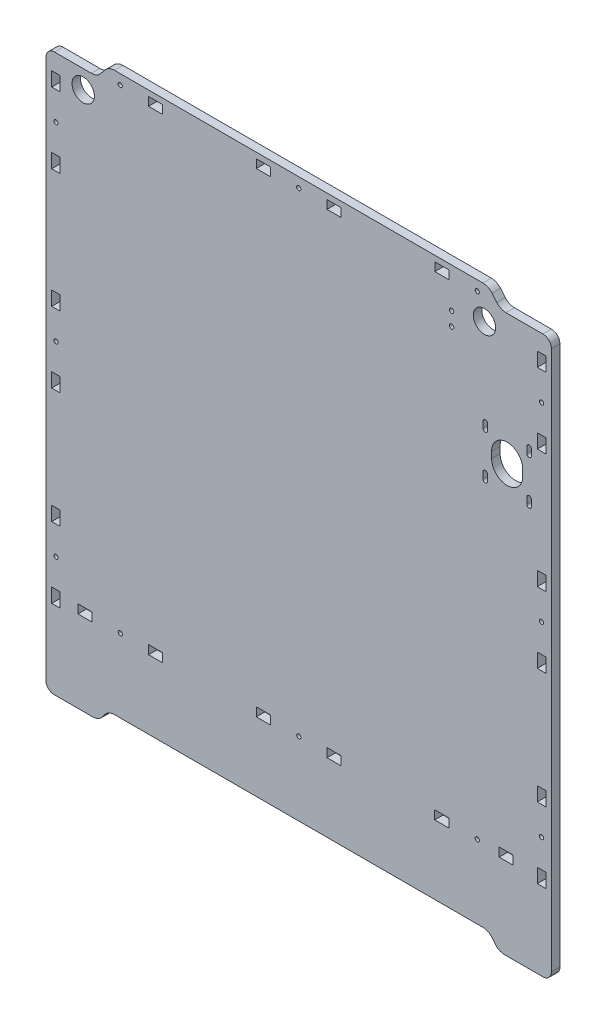
SolidWorks part; units mm, degrees
ref_plane "Спереди" through (0, 0, 0) normal (0, 0, 1) x (1, 0, 0)
ref_plane "Сверху" through (0, 0, 0) normal (0, 1, 0) x (1, 0, 0)
ref_plane "Справа" through (0, 0, 0) normal (1, 0, 0) x (0, 0, -1)
sketch "Эскиз1" plane through (0, 0, 0) normal (0, 0, 1) x (1, 0, 0)
  line L0 (133.6555, 83.4698) -> (133.6555, 87.9698)
  line L1 (133.6555, 118.9698) -> (133.6555, 114.4698)
  line L2 (130.4555, 83.4698) -> (130.4555, 87.9698)
  line L3 (158.5555, 98.9698) -> (158.5555, 103.4698)
  line L4 (130.4555, 118.9698) -> (130.4555, 114.4698)
  line L5 (161.4555, 118.9698) -> (161.4555, 114.4698)
  line L6 (164.6555, 118.9698) -> (164.6555, 114.4698)
  line L7 (136.5555, 98.9698) -> (136.5555, 103.4698)
  line L8 (161.4555, 83.4698) -> (161.4555, 87.9698)
  line L9 (164.6555, 83.4698) -> (164.6555, 87.9698)
  line L10 (-174.1809, 36.7423) -> (-174.1809, 46.7423)
  line L11 (106.3726, -142.2004) -> (96.3778, -142.2004)
  line L12 (96.3778, -142.2004) -> (96.3778, -136.0006)
  line L13 (96.3778, -136.0006) -> (106.3726, -136.0006)
  line L14 (106.3726, -136.0006) -> (106.3726, -142.2004)
  line L15 (151.7592, -142.2004) -> (141.91, -142.2004)
  line L16 (141.91, -142.2004) -> (141.91, -136.0006)
  line L17 (141.91, -136.0006) -> (151.7592, -136.0006)
  line L18 (151.7592, -136.0006) -> (151.7592, -142.2004)
  line L19 (-19.6709, 193.3023) -> (-29.6709, 193.3023)
  line L20 (-29.6709, 193.3023) -> (-29.6709, 199.3023)
  line L21 (-29.6709, 199.3023) -> (-19.6709, 199.3023)
  line L22 (-19.6709, 199.3023) -> (-19.6709, 193.3023)
  line L23 (30.3091, 193.3023) -> (20.3091, 193.3023)
  line L24 (20.3091, 193.3023) -> (20.3091, 199.3023)
  line L25 (20.3091, 199.3023) -> (30.3091, 199.3023)
  line L26 (30.3091, 199.3023) -> (30.3091, 193.3023)
  line L27 (-145.8164, -142.2004) -> (-155.6656, -142.2004)
  line L28 (-155.6656, -142.2004) -> (-155.6656, -136.0006)
  line L29 (-155.6656, -136.0006) -> (-145.8164, -136.0006)
  line L30 (-145.8164, -136.0006) -> (-145.8164, -142.2004)
  line L31 (-95.8164, -142.2004) -> (-105.7664, -142.2004)
  line L32 (-105.7664, -142.2004) -> (-105.7664, -136.0006)
  line L33 (-105.7664, -136.0006) -> (-95.8164, -136.0006)
  line L34 (-95.8164, -136.0006) -> (-95.8164, -142.2004)
  line L35 (-19.722, -142.199) -> (-29.6916, -142.199)
  line L36 (-29.6916, -142.199) -> (-29.6916, -135.9992)
  line L37 (-29.6916, -135.9992) -> (-19.722, -135.9992)
  line L38 (-19.722, -135.9992) -> (-19.722, -142.199)
  line L39 (30.2781, -142.199) -> (20.3037, -142.199)
  line L40 (20.3037, -142.199) -> (20.3037, -135.9992)
  line L41 (20.3037, -135.9992) -> (30.2781, -135.9992)
  line L42 (30.2781, -135.9992) -> (30.2781, -142.199)
  line L43 (-174.1809, 46.7423) -> (-168.1809, 46.7423)
  line L44 (-168.1809, 46.7423) -> (-168.1809, 36.7423)
  line L45 (-168.1809, 36.7423) -> (-174.1809, 36.7423)
  line L46 (-174.1809, -13.2577) -> (-174.1809, -3.2577)
  line L47 (-174.1809, -3.2577) -> (-168.1809, -3.2577)
  line L48 (-168.1809, -3.2577) -> (-168.1809, -13.2577)
  line L49 (-168.1809, -13.2577) -> (-174.1809, -13.2577)
  line L50 (-174.1809, 170.9023) -> (-174.1809, 180.9023)
  line L51 (-174.1809, 180.9023) -> (-168.1809, 180.9023)
  line L52 (-168.1809, 180.9023) -> (-168.1809, 170.9023)
  line L53 (-168.1809, 170.9023) -> (-174.1809, 170.9023)
  line L54 (-174.1809, 120.9023) -> (-174.1809, 130.9023)
  line L55 (-174.1809, 130.9023) -> (-168.1809, 130.9023)
  line L56 (-168.1809, 130.9023) -> (-168.1809, 120.9023)
  line L57 (-168.1809, 120.9023) -> (-174.1809, 120.9023)
  line L58 (-174.1809, -94.9877) -> (-174.1809, -84.9877)
  line L59 (-174.1809, -84.9877) -> (-168.1809, -84.9877)
  line L62 (-174.1809, -144.9777) -> (-174.1809, -134.9777)
  line L63 (-174.1809, -134.9777) -> (-168.1809, -134.9777)
  line L64 (-168.1809, -134.9777) -> (-168.1809, -144.9777)
  line L65 (-168.1809, -144.9777) -> (-174.1809, -144.9777)
  line L66 (168.8191, 36.7421) -> (168.8191, 46.7421)
  line L67 (168.8191, 46.7421) -> (174.8191, 46.7421)
  line L68 (174.8191, 46.7421) -> (174.8191, 36.7421)
  line L69 (174.8191, 36.7421) -> (168.8191, 36.7421)
  line L70 (168.8191, -13.2579) -> (168.8191, -3.2579)
  line L71 (168.8191, -3.2579) -> (174.8191, -3.2579)
  line L72 (174.8191, -3.2579) -> (174.8191, -13.2579)
  line L73 (174.8191, -13.2579) -> (168.8191, -13.2579)
  line L74 (168.8191, -94.9879) -> (168.8191, -84.9879)
  line L75 (168.8191, -84.9879) -> (174.8191, -84.9879)
  line L76 (174.8191, -84.9879) -> (174.8191, -94.9879)
  line L77 (174.8191, -94.9879) -> (168.8191, -94.9879)
  line L78 (168.8191, -144.9779) -> (168.8191, -134.9779)
  line L79 (168.8191, -134.9779) -> (174.8191, -134.9779)
  line L80 (174.8191, -134.9779) -> (174.8191, -144.9779)
  line L81 (174.8191, -144.9779) -> (168.8191, -144.9779)
  line L82 (168.8191, 170.9021) -> (168.8191, 180.9021)
  line L83 (168.8191, 180.9021) -> (174.8191, 180.9021)
  line L84 (175.1452, 170.9021) -> (168.8191, 170.9021)
  line L85 (168.8191, 120.9021) -> (168.8191, 130.9021)
  line L86 (168.8191, 130.9021) -> (174.8191, 130.9021)
  line L87 (174.8191, 130.9021) -> (174.8191, 120.9021)
  line L88 (174.8191, 120.9021) -> (168.8191, 120.9021)
  line L89 (-105.8209, 199.3023) -> (-95.8209, 199.3023)
  line L90 (-95.8209, 199.3023) -> (-95.8209, 193.3023)
  line L91 (-95.8209, 193.3023) -> (-105.8209, 193.3023)
  line L92 (-105.8209, 193.3023) -> (-105.8209, 199.3023)
  line L94 (96.4591, 193.3023) -> (96.4591, 199.3023)
  line L96 (146.7284, 193.3021) -> (172.7648, 193.3021)
  line L97 (106.4591, 193.3023) -> (96.4591, 193.3023)
  line L99 (-136.3916, 200.266) -> (-139.6874, 196.3386)
  line L100 (130.4099, 203.3023) -> (-129.8802, 203.3023)
  line L101 (136.9212, 200.266) -> (140.2171, 196.3385)
  line L102 (174.8191, 170.9781) -> (175.1452, 170.9021)
  line L104 (96.4591, 199.3023) -> (106.4591, 199.3023)
  line L105 (174.8191, 180.9021) -> (174.8191, 170.9781)
  line L106 (139.2171, -196.9614) -> (136.9212, -193.9418)
  line L107 (-129.8802, -190.9055) -> (130.4099, -190.9055)
  line L108 (-172.2352, -199.9977) -> (-145.1988, -199.9977)
  line L109 (-138.6874, -196.9614) -> (-136.3916, -193.9418)
  line L110 (172.7648, -199.9977) -> (145.7284, -199.9977)
  line L111 (-178.1809, 187.3023) -> (-178.1809, -195.6332)
  line L112 (178.8191, 187.3133) -> (178.8191, -193.9977)
  line L113 (-174.1809, -94.9877) -> (-168.1809, -94.9877)
  line L114 (-168.1809, -94.9877) -> (-168.1809, -84.9877)
  line L115 (-172.1809, 193.3023) -> (-146.1988, 193.3023)
  line L116 (106.4591, 199.3023) -> (106.4591, 193.3023)
  arc A0 (158.5555, 103.4698) -> (136.5555, 103.4698) centre (147.5555, 103.4698) ccw
  arc A1 (161.4555, 83.4698) -> (164.6555, 83.4698) centre (163.0555, 83.4698) ccw
  arc A2 (136.5555, 98.9698) -> (158.5555, 98.9698) centre (147.5555, 98.9698) ccw
  arc A3 (130.4555, 83.4698) -> (133.6555, 83.4698) centre (132.0555, 83.4698) ccw
  arc A4 (164.6555, 87.9698) -> (161.4555, 87.9698) centre (163.0555, 87.9698) ccw
  circle A5 centre (108.3191, 165.6023) radius 1.55
  circle A6 centre (108.3191, 175.3023) radius 1.55
  arc A7 (130.4555, 114.4698) -> (133.6555, 114.4698) centre (132.0555, 114.4698) ccw
  arc A8 (133.6555, 118.9698) -> (130.4555, 118.9698) centre (132.0555, 118.9698) ccw
  arc A9 (164.6555, 118.9698) -> (161.4555, 118.9698) centre (163.0555, 118.9698) ccw
  arc A10 (161.4555, 114.4698) -> (164.6555, 114.4698) centre (163.0555, 114.4698) ccw
  arc A11 (133.6555, 87.9698) -> (130.4555, 87.9698) centre (132.0555, 87.9698) ccw
  circle A12 centre (131.5191, 180.3023) radius 7.9
  circle A13 centre (-151.9809, 180.3023) radius 7.9
  arc A14 (-129.8802, 203.3023) -> (-136.3916, 200.266) centre (-129.8802, 194.8023) ccw
  arc A15 (-146.1988, 193.3023) -> (-139.6874, 196.3386) centre (-146.1988, 201.8023) ccw
  arc A17 (140.2171, 196.3385) -> (146.7284, 193.3021) centre (146.7286, 201.8021) ccw
  arc A18 (136.9212, 200.266) -> (130.4099, 203.3023) centre (130.4099, 194.8023) ccw
  arc A19 (178.8191, 187.3133) -> (172.7648, 193.3021) centre (172.8191, 187.3023) ccw
  arc A20 (136.9212, -193.9418) -> (130.4099, -190.9055) centre (130.4099, -199.4055) ccw
  arc A21 (-178.1809, -195.6332) -> (-172.2352, -199.9977) centre (-172.4074, -194.0002) ccw
  arc A22 (-145.1988, -199.9977) -> (-138.6874, -196.9614) centre (-145.1988, -191.4977) ccw
  arc A23 (139.2171, -196.9614) -> (145.7284, -199.9977) centre (145.7284, -191.4977) ccw
  arc A24 (-129.8802, -190.9055) -> (-136.3916, -193.9418) centre (-129.8802, -199.4055) ccw
  circle A25 centre (-171.1809, 150.9023) radius 1.5
  arc A26 (172.7648, -199.9977) -> (178.8191, -193.9977) centre (172.8191, -193.998) ccw
  circle A27 centre (-171.1809, 16.7423) radius 1.5
  circle A28 centre (171.8191, 150.9021) radius 1.5
  circle A29 centre (126.4591, 196.3023) radius 1.5
  circle A30 centre (-125.8209, 196.3023) radius 1.5
  circle A31 centre (0.3191, 196.3023) radius 1.5
  circle A32 centre (-125.7495, -139.0659) radius 1.5
  circle A33 centre (-171.1809, -114.9677) radius 1.5
  circle A34 centre (0.3757, -139.0659) radius 1.5
  circle A35 centre (126.4428, -139.0659) radius 1.5
  circle A36 centre (171.8191, -114.9679) radius 1.5
  circle A37 centre (171.8191, 16.7421) radius 1.5
  arc A38 (-178.1809, 187.3023) -> (-172.1809, 193.3023) centre (-172.1809, 187.3023) cw
  point P149 (159.2466, -199.9977)
  point P190 (-105.8209, 196.3023)
  point P191 (171.8191, -13.2579)
  point P192 (174.8191, -89.9879)
  point P193 (-100.8209, 193.3023)
  point P194 (20.3091, 196.3023)
  dimension "D9" = 15.8
  dimension "D24" = 8.5
  dimension "D25" = 8.5
  dimension "D26" = 6
  dimension "D27" = 8.5
  dimension "D28" = 8.5
  dimension "D29" = 4
  dimension "D30" = 6
  dimension "D32" = 12.4
  dimension "D40" = 20
  dimension "D82" = 9.7
  dimension "D83" = 28
  dimension "D84" = 70.5
  dimension "D3" = 10
  dimension "D4" = 20
  dimension "D5" = 20
  dimension "D6" = 10
  dimension "D7" = 6
  dimension "D8" = 6
  dimension "D10" = 74.16
  dimension "D11" = 10
  dimension "D12" = 6
  dimension "D13" = 20
  dimension "D14" = 6
  dimension "D15" = 10
  dimension "D16" = 71.73
  dimension "D17" = 6
  dimension "D18" = 10
  dimension "D19" = 20.01
  dimension "D20" = 10
  dimension "D21" = 20
  dimension "D22" = 403.3
  dimension "D23" = 19.98
  dimension "D31" = 10
  dimension "D33" = 10
  dimension "D34" = 55.02
  dimension "D35" = 6
  dimension "D36" = 10.0002
  dimension "D37" = 12.4
  dimension "D38" = 10
  dimension "D39" = 20
  dimension "D41" = 6
  dimension "D42" = 6
  dimension "D43" = 74.16
  dimension "D44" = 10
  dimension "D45" = 6
  dimension "D46" = 20
  dimension "D47" = 20
  dimension "D48" = 6
  dimension "D49" = 10
  dimension "D50" = 71.73
  dimension "D51" = 6
  dimension "D52" = 10
  dimension "D53" = 19.98
  dimension "D54" = 10
  dimension "D55" = 6
  dimension "D56" = 20.01
  dimension "D57" = 403.3
  dimension "D58" = 283.5
  dimension "D59" = 55.0198
  dimension "D60" = 357
  dimension "D61" = 26.2
  dimension "D62" = 47.3
  dimension "D63" = 23
  dimension "D64" = 23
  dimension "D65" = 7
  dimension "D66" = 4
  dimension "D67" = 4
  dimension "D68" = 7
  dimension "D69" = 4
  dimension "D70" = 4
  dimension "D71" = 7
  dimension "D72" = 4
  dimension "D73" = 4
  dimension "D74" = 7
  dimension "D75" = 4
  dimension "D76" = 4
  dimension "D77" = 7
  dimension "D78" = 4
  dimension "D79" = 4
  dimension "D80" = 7
  dimension "D81" = 4
  dimension "D85" = 7
  dimension "D86" = 4
  dimension "D87" = 10
  dimension "D88" = 6
  dimension "D89" = 6
  dimension "D90" = 10
  dimension "D91" = 4
  dimension "D92" = 7
  dimension "D93" = 10
  dimension "D94" = 6
  dimension "D95" = 4
  dimension "D96" = 7
  dimension "D97" = 4
  dimension "D98" = 6
  dimension "D99" = 52.36
  dimension "D100" = 20
  dimension "D101" = 66.15
  dimension "D102" = 52.36
  dimension "D103" = 20
  dimension "D104" = 10
  dimension "D105" = 66.15
  dimension "D106" = 178.5
  dimension "D107" = 19.99
  dimension "D108" = 19.99
extrude "Бобышка-Вытянуть1" add sketch "Эскиз1" along normal blind 6
